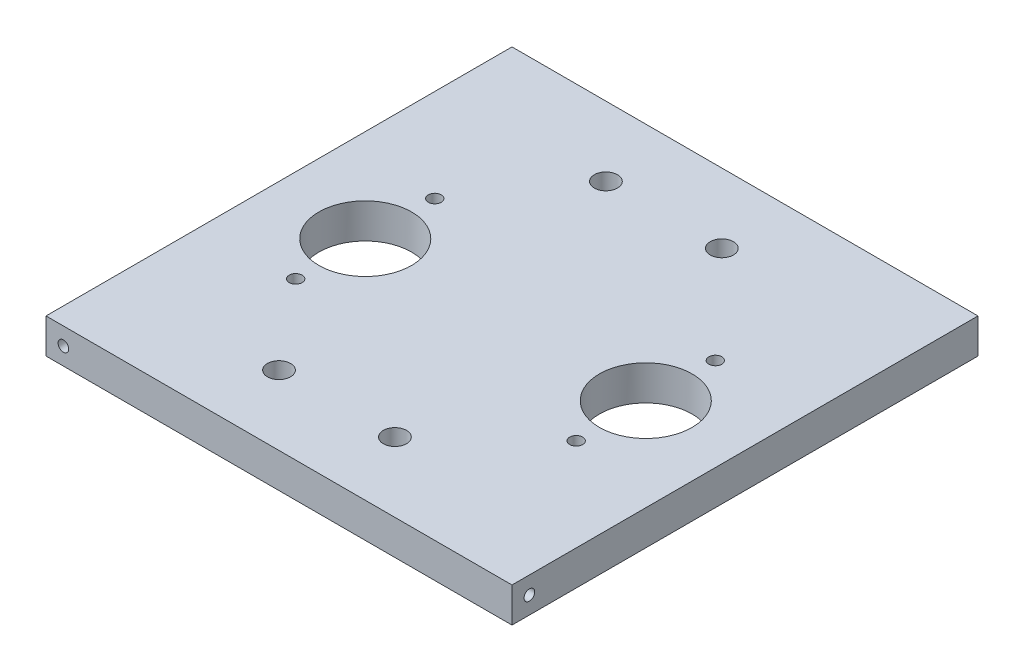
SolidWorks part; units mm, degrees
material "6061 Alloy"
ref_plane "Front" through (0, 0, 0) normal (0, 0, 1) x (1, 0, 0)
ref_plane "Top" through (0, 0, 0) normal (0, 1, 0) x (1, 0, 0)
ref_plane "Right" through (0, 0, 0) normal (1, 0, 0) x (0, 0, -1)
sketch "Sketch1" plane through (0, 0, 0) normal (0, 1, 0) x (1, 0, 0)
  line L1 (0, 0) -> (127.635, 0)
  line L2 (0, 0) -> (0, 127.635)
  line L3 (0, 127.635) -> (127.635, 127.635)
  line L4 (127.635, 0) -> (127.635, 127.635)
  dimension "D1" = 127.635
  dimension "D2" = 127.635
extrude "Main Plate" add sketch "Sketch1" along normal blind 9.525
sketch "Sketch2" plane through (0, 9.525, 0) normal (0, 1, 0) x (1, 0, 0)
  line L0 (0, 127.635) -> (0, 0) construction
  line L1 (127.635, 127.635) -> (0, 127.635) construction
  circle A0 centre (44.7675, 108.585) radius 3.175
  dimension "D1" = 6.35
  dimension "D2" = 44.7675
  dimension "D3" = 19.05
extrude "U-Bolt Hole" cut sketch "Sketch2" against normal blind 12.7
pattern_linear "U-Bolt Pattern" count 2 spacing 31.75 along (1, 0, 0) count 2 spacing 89.535 along (0, 0, 1) of "U-Bolt Hole"
sketch "Sketch3" plane through (0, 9.525, 0) normal (0, 1, 0) x (1, 0, 0)
  line L0 (0, 127.635) -> (0, 0) construction
  line L1 (0, 0) -> (127.635, 0) construction
  circle A0 centre (25.4, 42.9895) radius 1.778
  dimension "D1" = 3.556
  dimension "D2" = 25.4
  dimension "D3" = 42.9895
extrude "Raptor Bolt Hole" cut sketch "Sketch3" against normal blind 12.7
pattern_linear "Raptor Bolt Pattern" count 2 spacing 38.1 along (0, 0, -1) count 2 spacing 76.835 along (1, 0, 0) of "Raptor Bolt Hole"
sketch "Sketch4" plane through (0, 9.525, 0) normal (0, 1, 0) x (1, 0, 0)
  line L0 (0, 127.635) -> (0, 0) construction
  circle A0 centre (25.4, 62.0395) radius 12.7
  dimension "D1" = 25.4
  dimension "D2" = 19.05
  dimension "D3" = 25.4
extrude "Co2 Cylinder Hole" cut sketch "Sketch4" against normal blind 12.7
pattern_linear "Co2 Pattern" count 2 spacing 76.835 along (1, 0, 0) of "Co2 Cylinder Hole"
sketch "Sketch5" plane through (0, 0, 0) normal (0, 0, 1) x (1, 0, 0)
  line L0 (0, 9.525) -> (0, 0) construction
  line L1 (0, 0) -> (127.635, 0) construction
  circle A0 centre (4.7625, 4.7625) radius 1.4605
  dimension "D1" = 2.921
  dimension "D2" = 4.7625
  dimension "D3" = 4.7625
extrude "Frame attachment hole 1" cut sketch "Sketch5" against normal blind 12.7
sketch "Sketch6" plane through (0, 0, 0) normal (-1, 0, 0) x (0, 0, 1)
  line L2 (-127.635, 0) -> (0, 0) construction
  line L3 (-127.635, 9.525) -> (-127.635, 0) construction
  circle A0 centre (-122.8725, 4.7625) radius 1.4605
  dimension "D1" = 2.921
  dimension "D2" = 4.7625
  dimension "D3" = 4.7625
extrude "Frame attachment hole 2" cut sketch "Sketch6" against normal blind 12.7
sketch "Sketch7" plane through (0, 0, -127.635) normal (0, 0, -1) x (-1, 0, 0)
  line L2 (-127.635, 0) -> (0, 0) construction
  line L3 (-127.635, 9.525) -> (-127.635, 0) construction
  circle A0 centre (-122.8725, 4.7625) radius 1.4605
  dimension "D1" = 2.921
  dimension "D2" = 4.7625
  dimension "D3" = 4.7625
extrude "Frame attachment hole 3" cut sketch "Sketch7" against normal blind 12.7
sketch "Sketch8" plane through (127.635, 0, 0) normal (1, 0, 0) x (0, 0, -1)
  line L2 (0, 0) -> (127.635, 0) construction
  line L3 (0, 9.525) -> (0, 0) construction
  circle A0 centre (4.7625, 4.7625) radius 1.4605
  dimension "D1" = 2.921
  dimension "D2" = 4.7625
  dimension "D3" = 4.7625
extrude "Frame attachment hole 4" cut sketch "Sketch8" against normal blind 12.7
